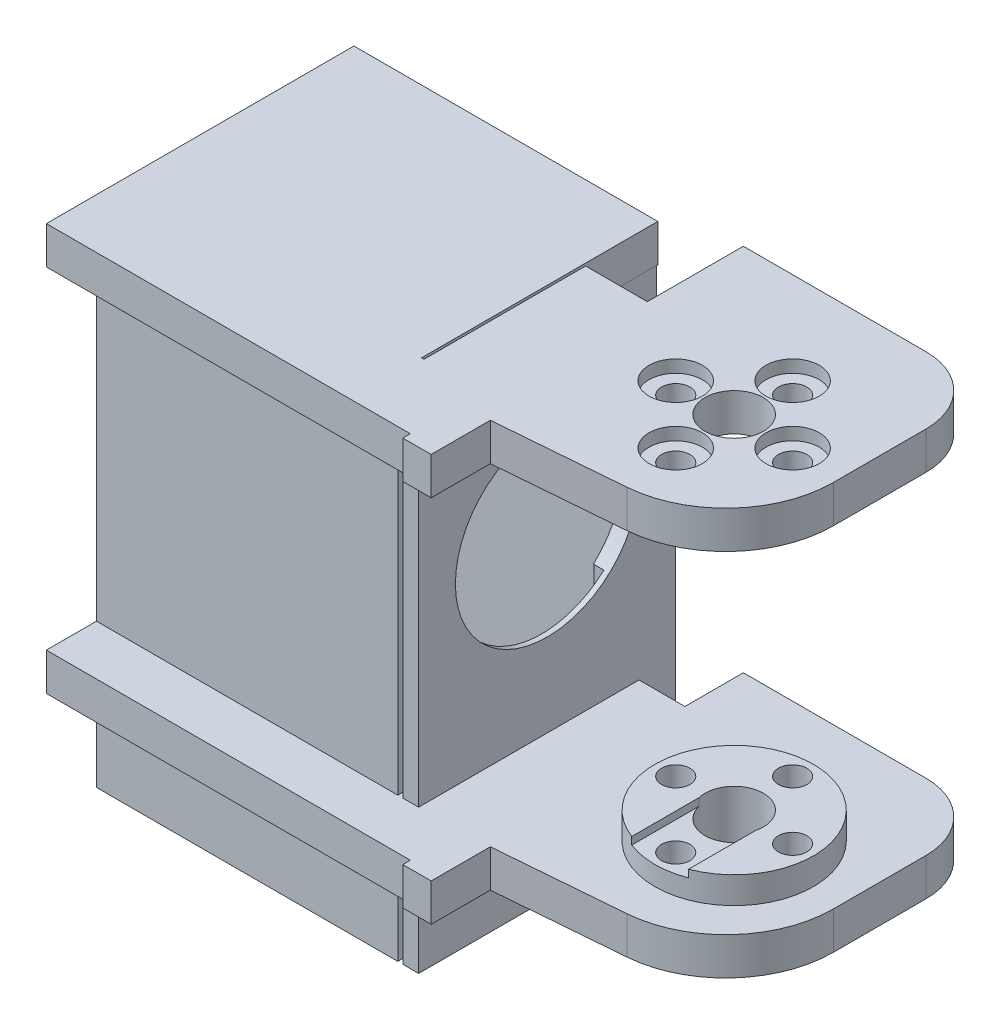
SolidWorks part; units mm, degrees
ref_plane "Front Plane" through (0, 0, 0) normal (0, 0, 1) x (1, 0, 0)
ref_plane "Top Plane" through (0, 0, 0) normal (0, 1, 0) x (1, 0, 0)
ref_plane "Right Plane" through (0, 0, 0) normal (1, 0, 0) x (0, 0, -1)
ref_plane "PY_p18_800" through (0, 18.8, 0) normal (0, 1, 0) x (1, 0, 0)
sketch "S_prism1" plane through (0, 18.8, 0) normal (0, 1, 0) x (1, 0, 0)
  line L0 (13, 10) -> (13, -1.1138)
  line L1 (1.1535, -13.9707) -> (-16.9, -15.45)
  line L2 (-16.9, -15.45) -> (-16.9, 18)
  line L3 (-16.9, 18) -> (5, 18)
  arc A0 (5, 18) -> (13, 10) centre (5.0002, 10.0002) cw
  arc A1 (13, -1.1138) -> (1.1535, -13.9707) centre (0.1, -1.1138) cw
extrude "Boss_1" add sketch "S_prism1" along normal blind 4.5
ref_plane "PY_m20_950" through (0, -20.95, 0) normal (0, 1, 0) x (1, 0, 0)
sketch "S_cyl2" plane through (0, -20.95, 0) normal (0, 1, 0) x (1, 0, 0)
  circle A0 centre (0, 0) radius 9.5
  dimension "D1_S_cyl2" = 19
extrude "Boss_2" add sketch "S_cyl2" along normal blind 3.2
ref_plane "PY_m25_450" through (0, -25.45, 0) normal (0, 1, 0) x (1, 0, 0)
sketch "S_prism3" plane through (0, -25.45, 0) normal (0, 1, 0) x (1, 0, 0)
  line L0 (13, 10) -> (13, -1.1138)
  line L1 (1.1535, -13.9707) -> (-16.9, -15.45)
  line L2 (-16.9, -15.45) -> (-16.9, 18)
  line L3 (-16.9, 18) -> (5, 18)
  arc A0 (5, 18) -> (13, 10) centre (5.0002, 10.0002) cw
  arc A1 (13, -1.1138) -> (1.1535, -13.9707) centre (0.1, -1.1138) cw
extrude "Boss_3" add sketch "S_prism3" along normal blind 4.5
sketch "S_prism4" plane through (0, 18.8, 0) normal (0, 1, 0) x (1, 0, 0)
  line L0 (-24.3, 6.5) -> (-16.8, 6.5)
  line L1 (-16.8, 6.5) -> (-16.8, -15.45)
  line L2 (-16.8, -15.45) -> (-24.3, -15.45)
  line L3 (-24.3, -15.45) -> (-24.3, 6.5)
extrude "Boss_4" add sketch "S_prism4" along normal blind 4.5
sketch "S_prism5" plane through (0, 18.8, 0) normal (0, 1, 0) x (1, 0, 0)
  line L0 (-61, -12.85) -> (-16.8, -12.85)
  line L1 (-16.8, -12.85) -> (-16.8, -21.4)
  line L2 (-16.8, -21.4) -> (-61, -21.4)
  line L3 (-61, -21.4) -> (-61, -12.85)
extrude "Boss_5" add sketch "S_prism5" along normal blind 4.5
sketch "S_prism6" plane through (0, 18.8, 0) normal (0, 1, 0) x (1, 0, 0)
  line L0 (-61, 15.45) -> (-24.6, 15.45)
  line L1 (-24.6, 15.45) -> (-24.6, -15.45)
  line L2 (-24.6, -15.45) -> (-61, -15.45)
  line L3 (-61, -15.45) -> (-61, 15.45)
extrude "Boss_6" add sketch "S_prism6" along normal blind 4.5
sketch "S_prism7" plane through (0, 18.8, 0) normal (0, 1, 0) x (1, 0, 0)
  line L0 (-17.4, -14.4) -> (-14, -14.4)
  line L1 (-14, -14.4) -> (-14, -22.3)
  line L2 (-14, -22.3) -> (-17.4, -22.3)
  line L3 (-17.4, -22.3) -> (-17.4, -14.4)
extrude "Boss_7" add sketch "S_prism7" along normal blind 4.5
sketch "S_prism8" plane through (0, -25.45, 0) normal (0, 1, 0) x (1, 0, 0)
  line L0 (-24.3, 11) -> (-16.8, 11)
  line L1 (-16.8, 11) -> (-16.8, -15.45)
  line L2 (-16.8, -15.45) -> (-24.3, -15.45)
  line L3 (-24.3, -15.45) -> (-24.3, 11)
extrude "Boss_8" add sketch "S_prism8" along normal blind 4.5
sketch "S_prism9" plane through (0, -25.45, 0) normal (0, 1, 0) x (1, 0, 0)
  line L0 (-61, -12.85) -> (-16.8, -12.85)
  line L1 (-16.8, -12.85) -> (-16.8, -21.4)
  line L2 (-16.8, -21.4) -> (-61, -21.4)
  line L3 (-61, -21.4) -> (-61, -12.85)
extrude "Boss_9" add sketch "S_prism9" along normal blind 4.5
sketch "S_prism10" plane through (0, -25.45, 0) normal (0, 1, 0) x (1, 0, 0)
  line L0 (-17.4, -14.4) -> (-14, -14.4)
  line L1 (-14, -14.4) -> (-14, -22.3)
  line L2 (-14, -22.3) -> (-17.4, -22.3)
  line L3 (-17.4, -22.3) -> (-17.4, -14.4)
extrude "Boss_10" add sketch "S_prism10" along normal blind 4.5
ref_plane "PZ_m15_400" through (0, 0, -15.4) normal (0, 0, 1) x (1, 0, 0)
sketch "S_box11" plane through (0, 0, -15.4) normal (0, 0, 1) x (1, 0, 0)
  line L0 (-61, 10.7) -> (-24.9, 10.7)
  line L1 (-24.9, 10.7) -> (-24.9, 13.2)
  line L2 (-24.9, 13.2) -> (-61, 13.2)
  line L3 (-61, 13.2) -> (-61, 10.7)
  dimension "P1" = 61
  dimension "P2" = 10.7
  dimension "P3" = 24.9
  dimension "P4" = 10.7
  dimension "P5" = 24.9
  dimension "P6" = 13.2
  dimension "P7" = 61
  dimension "P8" = 13.2
extrude "Boss_11" add sketch "S_box11" along normal blind 30.8
sketch "S_box12" plane through (0, 0, -15.4) normal (0, 0, 1) x (1, 0, 0)
  line L0 (-61, -38.2) -> (-24.9, -38.2)
  line L1 (-24.9, -38.2) -> (-24.9, 13.2)
  line L2 (-24.9, 13.2) -> (-61, 13.2)
  line L3 (-61, 13.2) -> (-61, -38.2)
  dimension "P1" = 61
  dimension "P2" = 38.2
  dimension "P3" = 24.9
  dimension "P4" = 38.2
  dimension "P5" = 24.9
  dimension "P6" = 13.2
  dimension "P7" = 61
  dimension "P8" = 13.2
extrude "Boss_12" add sketch "S_box12" along normal blind 2.5
ref_plane "PZ_p12_900" through (0, 0, 12.9) normal (0, 0, 1) x (1, 0, 0)
sketch "S_box13" plane through (0, 0, 12.9) normal (0, 0, 1) x (1, 0, 0)
  line L0 (-61, -38.2) -> (-24.9, -38.2)
  line L1 (-24.9, -38.2) -> (-24.9, 13.2)
  line L2 (-24.9, 13.2) -> (-61, 13.2)
  line L3 (-61, 13.2) -> (-61, -38.2)
  dimension "P1" = 61
  dimension "P2" = 38.2
  dimension "P3" = 24.9
  dimension "P4" = 38.2
  dimension "P5" = 24.9
  dimension "P6" = 13.2
  dimension "P7" = 61
  dimension "P8" = 13.2
extrude "Boss_13" add sketch "S_box13" along normal blind 2.5
sketch "S_box14" plane through (0, 0, -15.4) normal (0, 0, 1) x (1, 0, 0)
  line L0 (-61, -38.2) -> (-56.4, -38.2)
  line L1 (-56.4, -38.2) -> (-56.4, 13.2)
  line L2 (-56.4, 13.2) -> (-61, 13.2)
  line L3 (-61, 13.2) -> (-61, -38.2)
  dimension "P1" = 61
  dimension "P2" = 38.2
  dimension "P3" = 56.4
  dimension "P4" = 38.2
  dimension "P5" = 56.4
  dimension "P6" = 13.2
  dimension "P7" = 61
  dimension "P8" = 13.2
extrude "Boss_14" add sketch "S_box14" along normal blind 30.8
sketch "S_box15" plane through (0, 0, -15.4) normal (0, 0, 1) x (1, 0, 0)
  line L0 (-24.3, -38.2) -> (-22.4, -38.2)
  line L1 (-22.4, -38.2) -> (-22.4, 15.9)
  line L2 (-22.4, 15.9) -> (-24.3, 15.9)
  line L3 (-24.3, 15.9) -> (-24.3, -38.2)
  dimension "P1" = 24.3
  dimension "P2" = 38.2
  dimension "P3" = 22.4
  dimension "P4" = 38.2
  dimension "P5" = 22.4
  dimension "P6" = 15.9
  dimension "P7" = 24.3
  dimension "P8" = 15.9
extrude "Boss_15" add sketch "S_box15" along normal blind 30.8
ref_plane "PZ_m15_380" through (0, 0, -15.38) normal (0, 0, 1) x (1, 0, 0)
sketch "S_box16" plane through (0, 0, -15.38) normal (0, 0, 1) x (1, 0, 0)
  line L0 (-60.93, 12.9) -> (-24.67, 12.9)
  line L1 (-24.67, 12.9) -> (-24.67, 18.9)
  line L2 (-24.67, 18.9) -> (-60.93, 18.9)
  line L3 (-60.93, 18.9) -> (-60.93, 12.9)
  dimension "P1" = 60.93
  dimension "P2" = 12.9
  dimension "P3" = 24.67
  dimension "P4" = 12.9
  dimension "P5" = 24.67
  dimension "P6" = 18.9
  dimension "P7" = 60.93
  dimension "P8" = 18.9
extrude "Boss_16" add sketch "S_box16" along normal blind 30.76
ref_plane "PY_p18_700" through (0, 18.7, 0) normal (0, 1, 0) x (1, 0, 0)
sketch "S_hole17" plane through (0, 18.7, 0) normal (0, 1, 0) x (1, 0, 0)
  circle A0 centre (0, 0) radius 3.5
  dimension "D1_S_hole17" = 7
extrude "Hole_17" cut sketch "S_hole17" along normal blind 4.7
sketch "S_hole18" plane through (0, 18.7, 0) normal (0, 1, 0) x (1, 0, 0)
  circle A0 centre (7, 0) radius 1.7
  dimension "D1_S_hole18" = 3.4
  dimension "P2" = 7
extrude "Hole_18" cut sketch "S_hole18" along normal blind 4.7
sketch "S_hole19" plane through (0, 18.7, 0) normal (0, 1, 0) x (1, 0, 0)
  circle A0 centre (0, -7) radius 1.7
  dimension "D1_S_hole19" = 3.4
  dimension "P2" = 7
extrude "Hole_19" cut sketch "S_hole19" along normal blind 4.7
sketch "S_hole20" plane through (0, 18.7, 0) normal (0, 1, 0) x (1, 0, 0)
  circle A0 centre (-7, 0) radius 1.7
  dimension "D1_S_hole20" = 3.4
  dimension "P2" = 7
extrude "Hole_20" cut sketch "S_hole20" along normal blind 4.7
sketch "S_hole21" plane through (0, 18.7, 0) normal (0, 1, 0) x (1, 0, 0)
  circle A0 centre (0, 7) radius 1.7
  dimension "D1_S_hole21" = 3.4
  dimension "P2" = 7
extrude "Hole_21" cut sketch "S_hole21" along normal blind 4.7
ref_plane "PY_p21_800" through (0, 21.8, 0) normal (0, 1, 0) x (1, 0, 0)
sketch "S_hole22" plane through (0, 21.8, 0) normal (0, 1, 0) x (1, 0, 0)
  circle A0 centre (7, 0) radius 3.2
  dimension "D1_S_hole22" = 6.4
  dimension "P2" = 7
extrude "Hole_22" cut sketch "S_hole22" along normal blind 1.6
sketch "S_hole23" plane through (0, 21.8, 0) normal (0, 1, 0) x (1, 0, 0)
  circle A0 centre (0, -7) radius 3.2
  dimension "D1_S_hole23" = 6.4
  dimension "P2" = 7
extrude "Hole_23" cut sketch "S_hole23" along normal blind 1.6
sketch "S_hole24" plane through (0, 21.8, 0) normal (0, 1, 0) x (1, 0, 0)
  circle A0 centre (-7, 0) radius 3.2
  dimension "D1_S_hole24" = 6.4
  dimension "P2" = 7
extrude "Hole_24" cut sketch "S_hole24" along normal blind 1.6
sketch "S_hole25" plane through (0, 21.8, 0) normal (0, 1, 0) x (1, 0, 0)
  circle A0 centre (0, 7) radius 3.2
  dimension "D1_S_hole25" = 6.4
  dimension "P2" = 7
extrude "Hole_25" cut sketch "S_hole25" along normal blind 1.6
ref_plane "PY_m25_550" through (0, -25.55, 0) normal (0, 1, 0) x (1, 0, 0)
sketch "S_hole26" plane through (0, -25.55, 0) normal (0, 1, 0) x (1, 0, 0)
  circle A0 centre (0, 0) radius 3.5
  dimension "D1_S_hole26" = 7
extrude "Hole_26" cut sketch "S_hole26" along normal blind 7.9
sketch "S_hole27" plane through (0, -25.55, 0) normal (0, 1, 0) x (1, 0, 0)
  circle A0 centre (7, 0) radius 1.7
  dimension "D1_S_hole27" = 3.4
  dimension "P2" = 7
extrude "Hole_27" cut sketch "S_hole27" along normal blind 7.9
sketch "S_hole28" plane through (0, -25.55, 0) normal (0, 1, 0) x (1, 0, 0)
  circle A0 centre (0, -7) radius 1.7
  dimension "D1_S_hole28" = 3.4
  dimension "P2" = 7
extrude "Hole_28" cut sketch "S_hole28" along normal blind 7.9
sketch "S_hole29" plane through (0, -25.55, 0) normal (0, 1, 0) x (1, 0, 0)
  circle A0 centre (-7, 0) radius 1.7
  dimension "D1_S_hole29" = 3.4
  dimension "P2" = 7
extrude "Hole_29" cut sketch "S_hole29" along normal blind 7.9
sketch "S_hole30" plane through (0, -25.55, 0) normal (0, 1, 0) x (1, 0, 0)
  circle A0 centre (0, 7) radius 1.7
  dimension "D1_S_hole30" = 3.4
  dimension "P2" = 7
extrude "Hole_30" cut sketch "S_hole30" along normal blind 7.9
sketch "S_hole31" plane through (0, -25.55, 0) normal (0, 1, 0) x (1, 0, 0)
  circle A0 centre (7, 0) radius 3.2
  dimension "D1_S_hole31" = 6.4
  dimension "P2" = 7
extrude "Hole_31" cut sketch "S_hole31" along normal blind 2.1
sketch "S_hole32" plane through (0, -25.55, 0) normal (0, 1, 0) x (1, 0, 0)
  circle A0 centre (0, -7) radius 3.2
  dimension "D1_S_hole32" = 6.4
  dimension "P2" = 7
extrude "Hole_32" cut sketch "S_hole32" along normal blind 2.1
sketch "S_hole33" plane through (0, -25.55, 0) normal (0, 1, 0) x (1, 0, 0)
  circle A0 centre (-7, 0) radius 3.2
  dimension "D1_S_hole33" = 6.4
  dimension "P2" = 7
extrude "Hole_33" cut sketch "S_hole33" along normal blind 2.1
sketch "S_hole34" plane through (0, -25.55, 0) normal (0, 1, 0) x (1, 0, 0)
  circle A0 centre (0, 7) radius 3.2
  dimension "D1_S_hole34" = 6.4
  dimension "P2" = 7
extrude "Hole_34" cut sketch "S_hole34" along normal blind 2.1
sketch "S_cut35" plane through (0, 0, 0) normal (0, 0, 1) x (1, 0, 0)
  line L0 (-3.4, -18.65) -> (3.4, -18.65)
  line L1 (3.4, -18.65) -> (3.4, -17.65)
  line L2 (3.4, -17.65) -> (-3.4, -17.65)
  line L3 (-3.4, -17.65) -> (-3.4, -18.65)
  dimension "P1" = 3.4
  dimension "P2" = 18.65
  dimension "P3" = 3.4
  dimension "P4" = 18.65
  dimension "P5" = 3.4
  dimension "P6" = 17.65
  dimension "P7" = 3.4
  dimension "P8" = 17.65
extrude "Pocket_35" cut sketch "S_cut35" along normal blind 10
ref_plane "PX_m61_100" through (-61.1, 0, 0) normal (1, 0, 0) x (0, 0, -1)
sketch "S_hole36" plane through (-61.1, 0, 0) normal (1, 0, 0) x (0, 0, -1)
  circle A0 centre (0, 0) radius 10.5
  dimension "D1_S_hole36" = 21
extrude "Hole_36" cut sketch "S_hole36" along normal blind 4.8
ref_plane "PZ_m9_700" through (0, 0, -9.7) normal (0, 0, 1) x (1, 0, 0)
sketch "S_cut37" plane through (0, 0, -9.7) normal (0, 0, 1) x (1, 0, 0)
  line L0 (-61.1, -30.4) -> (-56.35, -30.4)
  line L1 (-56.35, -30.4) -> (-56.35, -10.9)
  line L2 (-56.35, -10.9) -> (-61.1, -10.9)
  line L3 (-61.1, -10.9) -> (-61.1, -30.4)
  dimension "P1" = 61.1
  dimension "P2" = 30.4
  dimension "P3" = 56.35
  dimension "P4" = 30.4
  dimension "P5" = 56.35
  dimension "P6" = 10.9
  dimension "P7" = 61.1
  dimension "P8" = 10.9
extrude "Pocket_37" cut sketch "S_cut37" along normal blind 19.4
sketch "S_cut38" plane through (0, 0, -9.7) normal (0, 0, 1) x (1, 0, 0)
  line L0 (-61.1, -38.7) -> (-56.35, -38.7)
  line L1 (-56.35, -38.7) -> (-56.35, -30.4)
  line L2 (-56.35, -30.4) -> (-61.1, -30.4)
  line L3 (-61.1, -30.4) -> (-61.1, -38.7)
  dimension "P1" = 61.1
  dimension "P2" = 38.7
  dimension "P3" = 56.35
  dimension "P4" = 38.7
  dimension "P5" = 56.35
  dimension "P6" = 30.4
  dimension "P7" = 61.1
  dimension "P8" = 30.4
extrude "Pocket_38" cut sketch "S_cut38" along normal blind 19.4
ref_plane "PZ_m3_500" through (0, 0, -3.5) normal (0, 0, 1) x (1, 0, 0)
sketch "S_cut39" plane through (0, 0, -3.5) normal (0, 0, 1) x (1, 0, 0)
  line L0 (-61.1, -11) -> (-56.35, -11)
  line L1 (-56.35, -11) -> (-56.35, 0)
  line L2 (-56.35, 0) -> (-61.1, 0)
  line L3 (-61.1, 0) -> (-61.1, -11)
  dimension "P1" = 61.1
  dimension "P2" = 11
  dimension "P3" = 56.35
  dimension "P4" = 11
  dimension "P5" = 56.35
  dimension "P6" = 61.1
extrude "Pocket_39" cut sketch "S_cut39" along normal blind 7
ref_plane "PZ_m15_900" through (0, 0, -15.9) normal (0, 0, 1) x (1, 0, 0)
sketch "S_cut40" plane through (0, 0, -15.9) normal (0, 0, 1) x (1, 0, 0)
  line L0 (-61.2, -10) -> (-58.3, -10)
  line L1 (-58.3, -10) -> (-58.3, 10)
  line L2 (-58.3, 10) -> (-61.2, 10)
  line L3 (-61.2, 10) -> (-61.2, -10)
  dimension "P1" = 61.2
  dimension "P2" = 10
  dimension "P3" = 58.3
  dimension "P4" = 10
  dimension "P5" = 58.3
  dimension "P6" = 10
  dimension "P7" = 61.2
  dimension "P8" = 10
extrude "Pocket_40" cut sketch "S_cut40" along normal blind 15.9
sketch "S_hole41" plane through (-61.1, 0, 0) normal (1, 0, 0) x (0, 0, -1)
  circle A0 centre (-10.25, -8.3) radius 1.1
  dimension "D1_S_hole41" = 2.2
  dimension "P2" = 10.25
  dimension "P3" = 8.3
extrude "Hole_41" cut sketch "S_hole41" along normal blind 4.8
sketch "S_hole42" plane through (-61.1, 0, 0) normal (1, 0, 0) x (0, 0, -1)
  circle A0 centre (-10.25, -8.3) radius 2.3
  dimension "D1_S_hole42" = 4.6
  dimension "P2" = 10.25
  dimension "P3" = 8.3
extrude "Hole_42" cut sketch "S_hole42" along normal blind 1.7
sketch "S_hole43" plane through (-61.1, 0, 0) normal (1, 0, 0) x (0, 0, -1)
  circle A0 centre (10.25, -32.75) radius 1.1
  dimension "D1_S_hole43" = 2.2
  dimension "P2" = 10.25
  dimension "P3" = 32.75
extrude "Hole_43" cut sketch "S_hole43" along normal blind 4.8
sketch "S_hole44" plane through (-61.1, 0, 0) normal (1, 0, 0) x (0, 0, -1)
  circle A0 centre (10.25, -32.75) radius 2.3
  dimension "D1_S_hole44" = 4.6
  dimension "P2" = 10.25
  dimension "P3" = 32.75
extrude "Hole_44" cut sketch "S_hole44" along normal blind 1.7
sketch "S_hole45" plane through (-61.1, 0, 0) normal (1, 0, 0) x (0, 0, -1)
  circle A0 centre (-10.25, -32.75) radius 1.1
  dimension "D1_S_hole45" = 2.2
  dimension "P2" = 10.25
  dimension "P3" = 32.75
extrude "Hole_45" cut sketch "S_hole45" along normal blind 4.8
sketch "S_hole46" plane through (-61.1, 0, 0) normal (1, 0, 0) x (0, 0, -1)
  circle A0 centre (-10.25, -32.75) radius 2.3
  dimension "D1_S_hole46" = 4.6
  dimension "P2" = 10.25
  dimension "P3" = 32.75
extrude "Hole_46" cut sketch "S_hole46" along normal blind 1.7
ref_plane "PX_m25_000" through (-25, 0, 0) normal (1, 0, 0) x (0, 0, -1)
sketch "S_hole47" plane through (-25, 0, 0) normal (1, 0, 0) x (0, 0, -1)
  circle A0 centre (0, 0) radius 11
  dimension "D1_S_hole47" = 22
extrude "Hole_47" cut sketch "S_hole47" along normal blind 2.7
ref_plane "PZ_m7_500" through (0, 0, -7.5) normal (0, 0, 1) x (1, 0, 0)
sketch "S_cut48" plane through (0, 0, -7.5) normal (0, 0, 1) x (1, 0, 0)
  line L0 (-24.9, -38.7) -> (-23.05, -38.7)
  line L1 (-23.05, -38.7) -> (-23.05, -8.1)
  line L2 (-23.05, -8.1) -> (-24.9, -8.1)
  line L3 (-24.9, -8.1) -> (-24.9, -38.7)
  dimension "P1" = 24.9
  dimension "P2" = 38.7
  dimension "P3" = 23.05
  dimension "P4" = 38.7
  dimension "P5" = 23.05
  dimension "P6" = 8.1
  dimension "P7" = 24.9
  dimension "P8" = 8.1
extrude "Pocket_48" cut sketch "S_cut48" along normal blind 15
sketch "S_pcut49" plane through (-61.1, 0, 0) normal (1, 0, 0) x (0, 0, -1)
  line L0 (16, -38.8) -> (16, -28.6)
  line L1 (16, -28.6) -> (5.8, -38.8)
  line L2 (5.8, -38.8) -> (16, -38.8)
extrude "Cut_49" cut sketch "S_pcut49" along normal blind 36.3
equation "\"plate_t\" = 3"
equation "\"clearance\" = 0.5"
